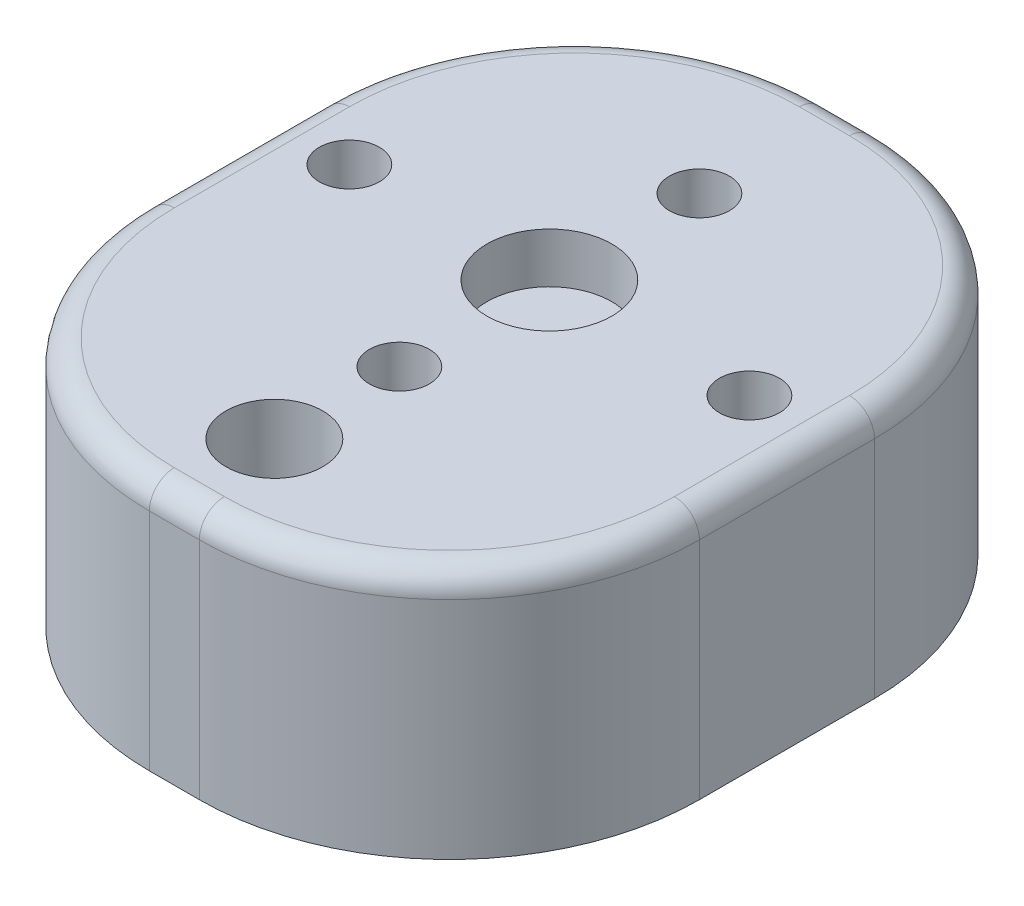
SolidWorks part; units mm, degrees
ref_plane "Plan de face" through (0, 0, 0) normal (0, 0, 1) x (1, 0, 0)
ref_plane "Plan de dessus" through (0, 0, 0) normal (0, 1, 0) x (1, 0, 0)
ref_plane "Plan de droite" through (0, 0, 0) normal (1, 0, 0) x (0, 0, -1)
sketch "Esquisse1" plane through (0, 0, 0) normal (0, 0, 1) x (1, 0, 0)
  line L1 (0, 0) -> (22, 0)
  line L2 (0, 0) -> (0, 10)
  line L3 (0, 10) -> (22, 10)
  line L4 (22, 0) -> (22, 10)
  arc A0 (6, 0) -> (16, 0) centre (11, 0) cw
  dimension "D3" = 5
  dimension "D1" = 22
  dimension "D2" = 10
  dimension "D4" = 11
extrude "Boss.-Extru.1" add sketch "Esquisse1" along normal blind 22 contours L1 A0 L4 L3 L2 region at (11, 5.6253, 0)
hole_wizard "Dégagement M21" positions "Esquisse2" profile "Esquisse4" hole size "M2" standard "ISO" end condition through all
sketch "Esquisse2" plane through (0, 10, 0) normal (0, 1, 0) x (1, 0, 0)
  line L0 (0, -22) -> (0, 0) construction
  line L3 (11, 5.9602) -> (11, -38.6048) construction
  line L5 (0, 0) -> (22, 0) construction
  point P0 (11, -6)
  point P2 (11, -18)
  point P4 (3, -12)
  point P6 (19, -12)
  dimension "D1" = 11
  dimension "D2" = 12
  dimension "D3" = 16
  dimension "D4" = 11
  dimension "D5" = 8
  dimension "D6" = 6
  dimension "D7" = 6
  dimension "D8" = 6
sketch "Esquisse4" plane through (11, 10, 6) normal (1, 0, 0) x (0, 0, 1)
  line L0 (0, 0) -> (0, 10)
  line L1 (0, 10) -> (1.2, 10)
  line L2 (1.2, 10) -> (1.2, 0)
  line L5 (1.2, 0) -> (0, 0)
  line L11 (0, -6.35) -> (0, 107.95) construction
  dimension "Diamètre du perçage jusqu'au prochain" = 2.4
  dimension "Profondeur du perçage jusqu'au prochain" = 10
sketch "Esquisse5" plane through (0, 0, 22) normal (0, 0, 1) x (1, 0, 0)
  line L1 (0, 0) -> (22, 0)
  line L2 (0, 0) -> (0, 10)
  line L3 (0, 10) -> (22, 10)
  line L4 (22, 0) -> (22, 10)
extrude "Boss.-Extru.2" add sketch "Esquisse5" along normal blind 5
fillet "Congé1" radius 10 4 edges at (0, 5, 0) (0, 5, 27) (22, 5, 0) (22, 5, 27)
fillet "Congé3" radius 1 8 edges at (11, 10, 27) (11, 10, 0) (2.9289, 10, 2.9289) (0, 10, 13.5) (2.9289, 10, 24.0711) (19.0711, 10, 24.0711) (22, 10, 13.5) (19.0711, 10, 2.9289)
sketch "Esquisse10" plane through (0, 0, 22) normal (0, 0, -1) x (-1, 0, 0)
  line L0 (-6, 0) -> (-16, 0) construction
  line L1 (-7, 0) -> (-15, 0)
  arc A0 (-15, 0) -> (-7, 0) centre (-11, 0) cw
  dimension "D1" = 4
  dimension "D2" = 5
extrude "Enlèv. mat.-Extru.2" cut sketch "Esquisse10" against normal blind 3
sketch "Esquisse12" plane through (0, 10, 0) normal (0, 1, 0) x (1, 0, 0)
  line L0 (0, -17) -> (0, -10) construction
  line L2 (10, 0) -> (12, 0) construction
  circle A0 centre (11, -23) radius 1.9376
  dimension "D1" = 11
  dimension "D2" = 23
extrude "Enlèv. mat.-Extru.3" cut sketch "Esquisse12" against normal through all
sketch "Esquisse13" plane through (0, 10, 0) normal (0, 1, 0) x (1, 0, 0)
  line L0 (22, -10) -> (22, -17) construction
  line L1 (10, 0) -> (12, 0) construction
  circle A0 centre (11, -12) radius 2.5
  dimension "D3" = 5
  dimension "D1" = 11
  dimension "D2" = 12
extrude "Enlèv. mat.-Extru.4" cut sketch "Esquisse13" against normal blind 2
equation "\"D4@Esquisse1\"=\"D1@Esquisse1\"/2"
